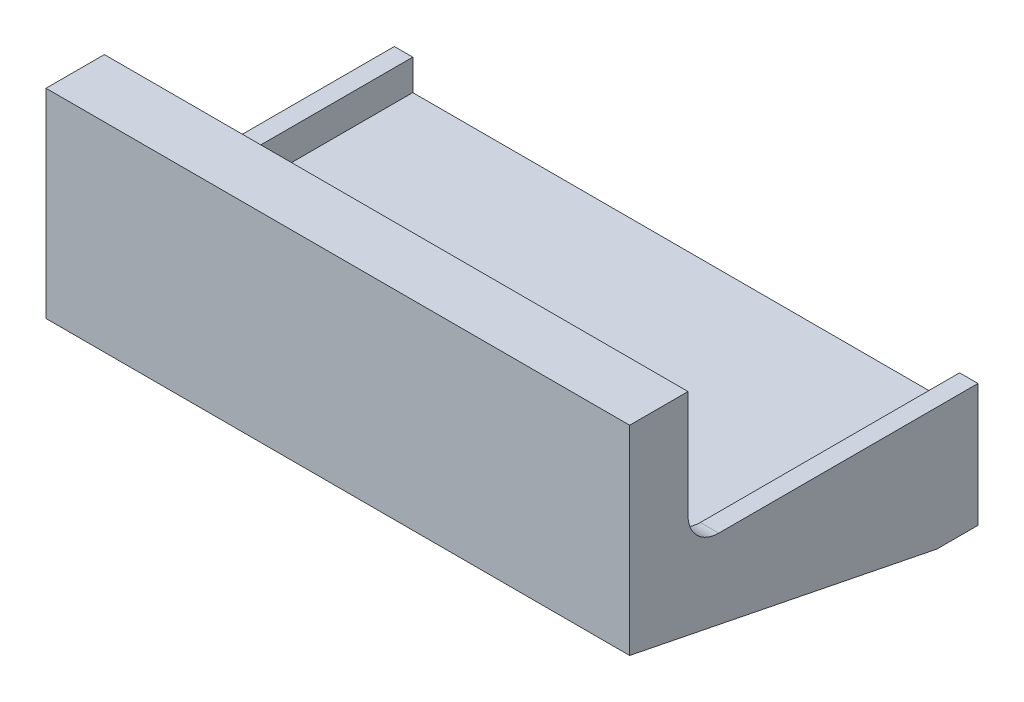
SolidWorks part; units mm, degrees
material "PLA"
ref_plane "Front Plane" through (0, 0, 0) normal (0, 0, 1) x (1, 0, 0)
ref_plane "Top Plane" through (0, 0, 0) normal (0, 1, 0) x (1, 0, 0)
ref_plane "Right Plane" through (0, 0, 0) normal (1, 0, 0) x (0, 0, -1)
sketch "Sketch1" plane through (0, 0, 0) normal (0, 0, 1) x (1, 0, 0)
  line L0 (-149, 38.5) -> (-149, 15.5) construction
  line L1 (-149, 38.5) -> (-149, 15.5) construction
  line L2 (-61, 15.5) -> (-61, 38.5) construction
  line L3 (-61, 15.5) -> (-61, 38.5) construction
  line L4 (-62, 15.5) -> (-148, 15.5) construction
  line L5 (-61, 15.5) -> (-149, 15.5) construction
  line L6 (-60.5, 15) -> (-60.5, 20)
  line L7 (-60.5, 15) -> (-149.5, 15)
  line L8 (-149.5, 20) -> (-149.5, 15)
  line L9 (-60.5, 15) -> (-60.5, 38.5) construction
  line L10 (-60.5, 20) -> (-57.5, 20)
  line L11 (-57.5, 20) -> (-57.5, 0)
  line L12 (-57.5, 0) -> (-152.5, 0)
  line L13 (-152.5, 0) -> (-152.5, 20)
  line L14 (-149.5, 38.5) -> (-149.5, 15) construction
  line L15 (-152.5, 20) -> (-149.5, 20)
  line L16 (0, 0) -> (-320, 0) construction
  dimension "D2" = 95
  dimension "D3" = 20
  dimension "D1" = 0.5
extrude "Boss-Extrude1" add sketch "Sketch1" along normal offset from surface (53.2 mm away) 0.5 offset beyond the face yes
sketch "Sketch2" plane through (0, 0, 53.2) normal (0, 0, 1) x (1, 0, 0)
  line L1 (-152.5, 20) -> (-57.5, 20)
  line L2 (-152.5, 20) -> (-152.5, 0)
  line L3 (-152.5, 0) -> (-57.5, 0)
  line L4 (-57.5, 20) -> (-57.5, 0)
extrude "Boss-Extrude2" add sketch "Sketch2" along normal blind 3.5
chamfer "Chamfer1" distance 50 distance2 10 1 edges at (-105, 0, 56.7) first distance on face at (-105, 0, 28.35)
sketch "Sketch3" plane through (0, 0, 56.7) normal (0, 0, 1) x (1, 0, 0)
  line L0 (-152.5, 20) -> (-57.5, 20)
  line L1 (-152.5, 20) -> (-152.5, 42.4638)
  line L2 (-57.5, 20) -> (-57.5, 42.4638)
  line L3 (-152.5, 42.4638) -> (-57.5, 42.4638)
  line L4 (-149, 15.5) -> (-149, 38.5) construction
  line L7 (-149, 20) -> (-149, 38.5) construction
  line L8 (-148, 38.5) -> (-62, 38.5) construction
  line L9 (-149, 38.5) -> (-61, 38.5) construction
  line L10 (-61, 38.5) -> (-61, 15.5) construction
  line L11 (-61, 38.5) -> (-61, 20) construction
  line L12 (-57.5, 20) -> (-152.5, 20) construction
  line L13 (-149.5, 20) -> (-149.5, 39)
  line L14 (-149.5, 39) -> (-60.5, 39)
  line L15 (-60.5, 39) -> (-60.5, 20)
  line M11 (-57.5, 20) -> (-152.5, 20)
  dimension "D1" = 0.5
extrude "Boss-Extrude3" add sketch "Sketch3" against normal up to surface (3.5 mm away) contours L15 L14 L13 L0 | L14 L15 L2 L3 L1 L0 L13 M11 region at (-151.5238, 31.2319, 56.7) region at (-105, 29.5, 56.7) up to face at (-105, 17.5, 53.2)
extrude "Boss-Extrude4" add sketch "Sketch3<3>" against normal blind 6 from surface contours L14 L15 L2 L3 L1 L0 L13 M11 region at (-151.5238, 31.2319, 56.7) starting at face at (-105, 24.366, 53.2)
sketch "Sketch3<3>" plane through (0, 0, 56.7) normal (0, 0, 1) x (1, 0, 0) same geometry as "Sketch3"
fillet "Fillet1" radius 5 2 edges at (-151, 20, 47.2) (-59, 20, 47.2)
sketch "Sketch4" plane through (0, 0, 0) normal (0, 0, -1) x (-1, 0, 0)
  point P0 (70, 5.6)
  point P1 (140, 5.6)
hole_wizard "Ø2.5mm Dowel Hole1" positions "Sketch4" profile "Sketch5" hole size "Ø2.5" standard "ANSI Metric"
sketch "Sketch5" plane through (-70, 5.6, 0) normal (1, 0, 0) x (0, 1, 0)
  line L0 (0, 0) -> (0, 7.4614)
  line L1 (0, 7.4614) -> (1.6, 6.5)
  line L2 (1.6, 6.5) -> (1.6, 0)
  line L5 (1.6, 0) -> (0, 0)
  line L10 (0, 7.4614) -> (-1.6, 6.5) construction
  line L11 (0, -6.35) -> (0, 107.95) construction
  dimension "Hole Dia." = 3.2
  dimension "Hole Depth" = 6.5
  dimension "Drill Angle" = 118
